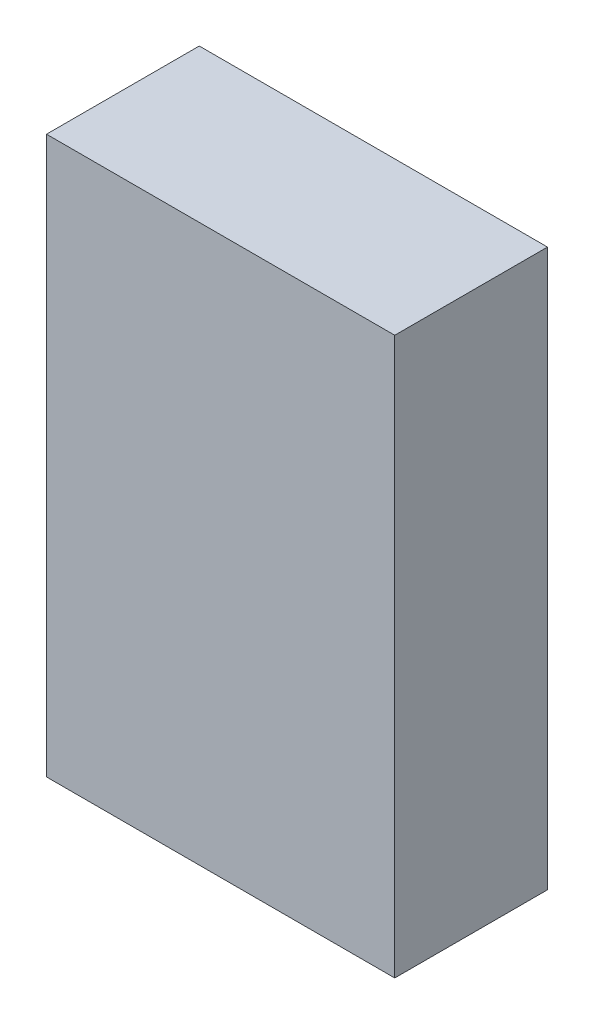
SolidWorks part; units mm, degrees
ref_plane "前视基准面" through (0, 0, 0) normal (0, 0, 1) x (1, 0, 0)
ref_plane "上视基准面" through (0, 0, 0) normal (0, 1, 0) x (1, 0, 0)
ref_plane "右视基准面" through (0, 0, 0) normal (1, 0, 0) x (0, 0, -1)
other "Configuration Table"
sketch "草图1" plane through (0, 0, 0) normal (0, 0, 1) x (1, 0, 0)
  line L0 (42.98, -20.38) -> (27.5617, -20.38) construction
  line L1 (64.1299, 121.75) -> (-23.29, 121.75)
  line L2 (64.1299, 121.75) -> (64.1299, -20.38)
  line L3 (64.1299, -20.38) -> (-23.29, -20.38)
  line L4 (-23.29, 121.75) -> (-23.29, -20.38)
  line L5 (-22.29, 116.75) -> (-22.29, 121.75) construction
  dimension "D1" = 1
extrude "凸台-拉伸1" add sketch "草图1" along normal blind 2
sketch "草图3" plane through (0, 0, 2) normal (0, 0, 1) x (1, 0, 0)
  line L0 (66.1299, -22.38) -> (66.1299, 123.75)
  line L1 (66.1299, 123.75) -> (-25.29, 123.75)
  line L2 (-25.29, 123.75) -> (-25.29, -22.38)
  line L3 (-25.29, -22.38) -> (66.1299, -22.38)
  line L4 (64.1299, -20.38) -> (64.1299, 121.75)
  line L5 (64.1299, 121.75) -> (-23.29, 121.75)
  line L6 (-23.29, 121.75) -> (-23.29, -20.38)
  line L7 (-23.29, -20.38) -> (64.1299, -20.38)
  line L8 (64.1299, -20.38) -> (64.1299, 121.75)
  line L9 (64.1299, 121.75) -> (-23.29, 121.75)
  line L10 (-23.29, 121.75) -> (-23.29, -20.38)
  line L11 (-23.29, -20.38) -> (64.1299, -20.38)
  dimension "D1" = 0
  dimension "D2" = 2
extrude "凸台-拉伸2" add sketch "草图3" against normal up to surface (40.1 mm away)
sketch "草图4" plane through (0, -22.38, 0) normal (0, -1, 0) x (1, 0, 0)
  line L8 (13.73, -15.6) -> (-13.73, -15.6)
  line L9 (-13.73, -15.6) -> (-13.73, -23.91)
  line L10 (-13.73, -23.91) -> (13.73, -23.91)
  line L11 (13.73, -23.91) -> (13.73, -15.6)
  line L12 (13.73, -15.6) -> (-13.73, -15.6)
  line L13 (-13.73, -15.6) -> (-13.73, -23.91)
  line L14 (-13.73, -23.91) -> (13.73, -23.91)
  line L15 (13.73, -23.91) -> (13.73, -15.6)
  line L16 (1.95, -4) -> (-15.95, -4) construction
  line L17 (1.95, 0) -> (-15.95, 0) construction
  line L18 (-15.95, -4) -> (-15.95, 0) construction
  line L19 (1.95, -4) -> (1.95, 0) construction
  line L20 (-15.95, -4) -> (1.95, -4)
  line L21 (1.95, -4) -> (1.95, 0)
  line L22 (1.95, 0) -> (-15.95, 0)
  line L23 (-15.95, 0) -> (-15.95, -4)
  arc A0 (31.8967, -17.4163) -> (31.8967, -22.0937) centre (26.48, -19.755) ccw construction
  arc A1 (31.8967, -22.0937) -> (31.8967, -17.4163) centre (32.78, -19.755) ccw construction
  arc A2 (31.8967, -17.4163) -> (31.8967, -22.0937) centre (26.48, -19.755) ccw
  arc A3 (31.8967, -22.0937) -> (31.8967, -17.4163) centre (32.78, -19.755) ccw
  dimension "D1" = 4
extrude "切除-拉伸1" cut sketch "草图4" against normal up to next
